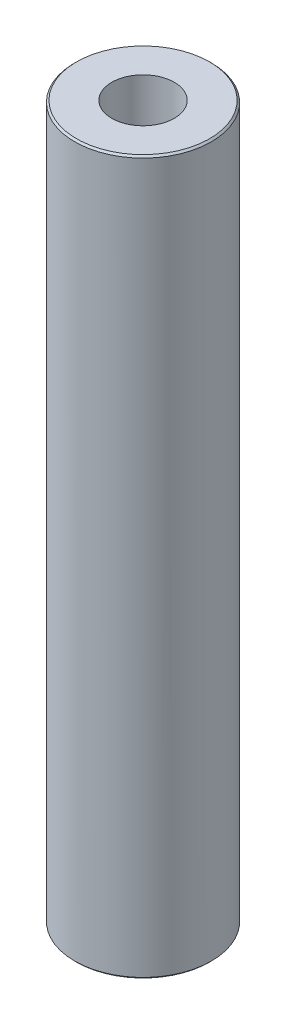
SolidWorks part; units mm, degrees
ref_plane "Front Plane" through (0, 0, 0) normal (0, 0, 1) x (1, 0, 0)
ref_plane "Top Plane" through (0, 0, 0) normal (0, 1, 0) x (1, 0, 0)
ref_plane "Right Plane" through (0, 0, 0) normal (1, 0, 0) x (0, 0, -1)
sketch "Sketch1" plane through (0, 0, 0) normal (0, 1, 0) x (1, 0, 0)
  circle A0 centre (0, 0) radius 57.5
  dimension "SHAFT_OD" = 115
extrude "Boss-Extrude1" add sketch "Sketch1" along normal blind 600
sketch "Sketch2" plane through (0, 0, 0) normal (0, 1, 0) x (1, 0, 0)
  circle A0 centre (0, 0) radius 26.3038
  dimension "BORE_D" = 52.6076
extrude "Cut-Extrude1" cut sketch "Sketch2" along normal through all
chamfer "Chamfer1" distance 1.4927 angle 45 2 edges at (0, 600, 57.5) (0, 0, 57.5)
